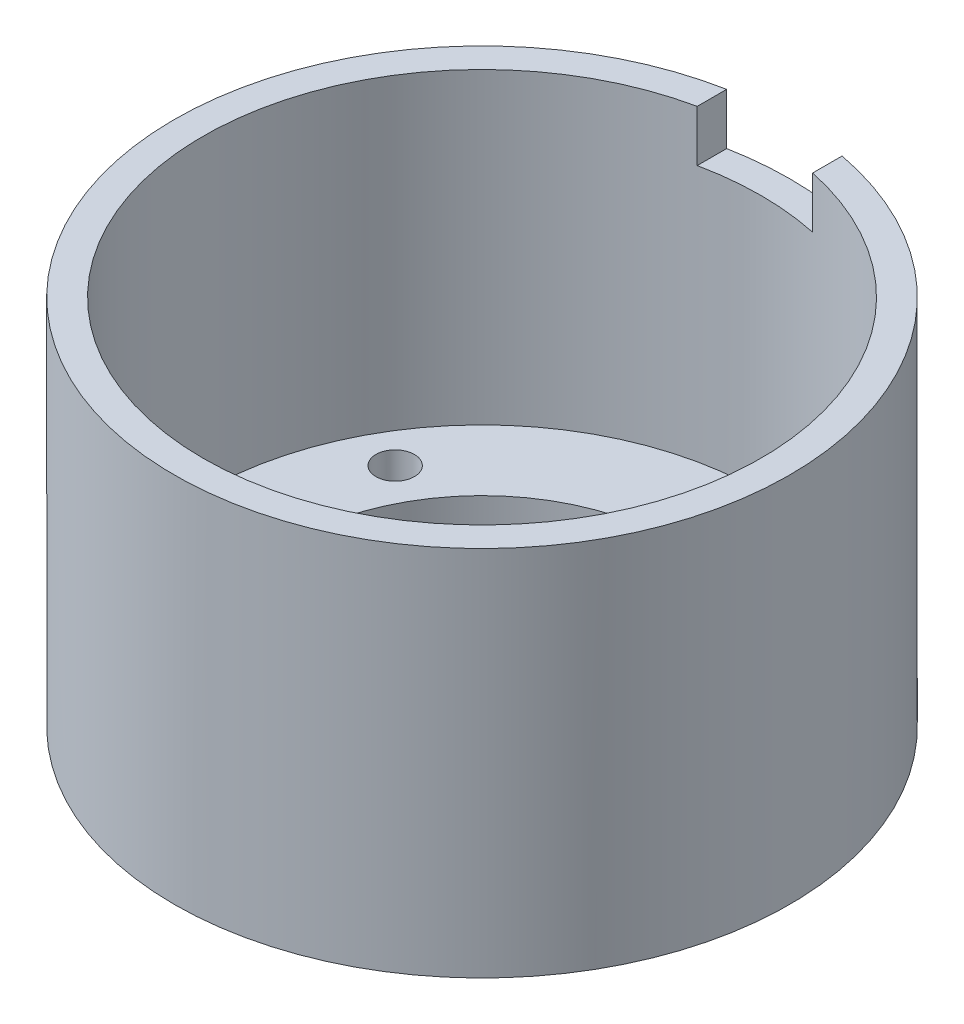
SolidWorks part; units mm, degrees
ref_plane "Front Plane" through (0, 0, 0) normal (0, 0, 1) x (1, 0, 0)
ref_plane "Top Plane" through (0, 0, 0) normal (0, 1, 0) x (1, 0, 0)
ref_plane "Right Plane" through (0, 0, 0) normal (1, 0, 0) x (0, 0, -1)
sketch "Sketch1" plane through (0, 0, 0) normal (0, 1, 0) x (1, 0, 0)
  circle A0 centre (0, 0) radius 24
  circle A1 centre (0, 0) radius 21.75
  dimension "D1" = 43.5
  dimension "D2" = 48
extrude "Boss-Extrude1" add sketch "Sketch1" along normal blind 24
sketch "Sketch2" plane through (0, 0, 0) normal (0, -1, 0) x (1, 0, 0)
  circle A0 centre (0, 0) radius 24
  circle A1 centre (0, 0) radius 15
  circle A2 centre (0, 0) radius 24 construction
  dimension "D1" = 30
extrude "Boss-Extrude2" add sketch "Sketch2" along normal blind 5
sketch "Sketch3" plane through (0, -5, 0) normal (0, -1, 0) x (1, 0, 0)
  circle A0 centre (0, 0) radius 18.5 construction
  circle A1 centre (0, 18.5) radius 2.5
  circle A2 centre (16.0215, -9.25) radius 2.5
  circle A3 centre (-16.0215, -9.25) radius 2.5
  dimension "D1" = 37
  dimension "D3" = 5
  dimension "D2" = 3
extrude "Cut-Extrude1" cut sketch "Sketch3" against normal blind 2
sketch "Sketch4" plane through (0, -3, 0) normal (0, -1, 0) x (1, 0, 0)
  circle A0 centre (0, 18.5) radius 1.5
  circle A1 centre (16.0215, -9.25) radius 1.5
  circle A2 centre (-16.0215, -9.25) radius 1.5
  dimension "D1" = 3
extrude "Cut-Extrude2" cut sketch "Sketch4" against normal through all
ref_plane "Plane1" through (0, 0, -24) normal (0, 0, -1) x (-1, 0, 0)
sketch "Sketch5" plane through (0, 0, -24) normal (0, 0, -1) x (-1, 0, 0)
  line L0 (24, 24) -> (-24, 24) construction
  line L1 (-4.5, 24) -> (4.5, 24)
  line L2 (-4.5, 24) -> (-4.5, 20)
  line L3 (-4.5, 20) -> (4.5, 20)
  line L4 (4.5, 24) -> (4.5, 20)
  point P6 (0, 20)
  dimension "D1" = 9
  dimension "D2" = 4
extrude "Cut-Extrude3" cut sketch "Sketch5" against normal up to surface (2.7206 mm away) up to face at (0, 24, 21.75)
sketch "Sketch6" plane through (0, 24, 0) normal (0, 1, 0) x (1, 0, 0)
  circle A6 centre (0, 0) radius 24
  circle A7 centre (0, 0) radius 21.75
  arc A8 (-4.5, 21.2794) -> (4.5, 21.2794) centre (0, 0) ccw construction
  arc A9 (-4.5, 23.5744) -> (4.5, 23.5744) centre (0, 0) ccw construction
